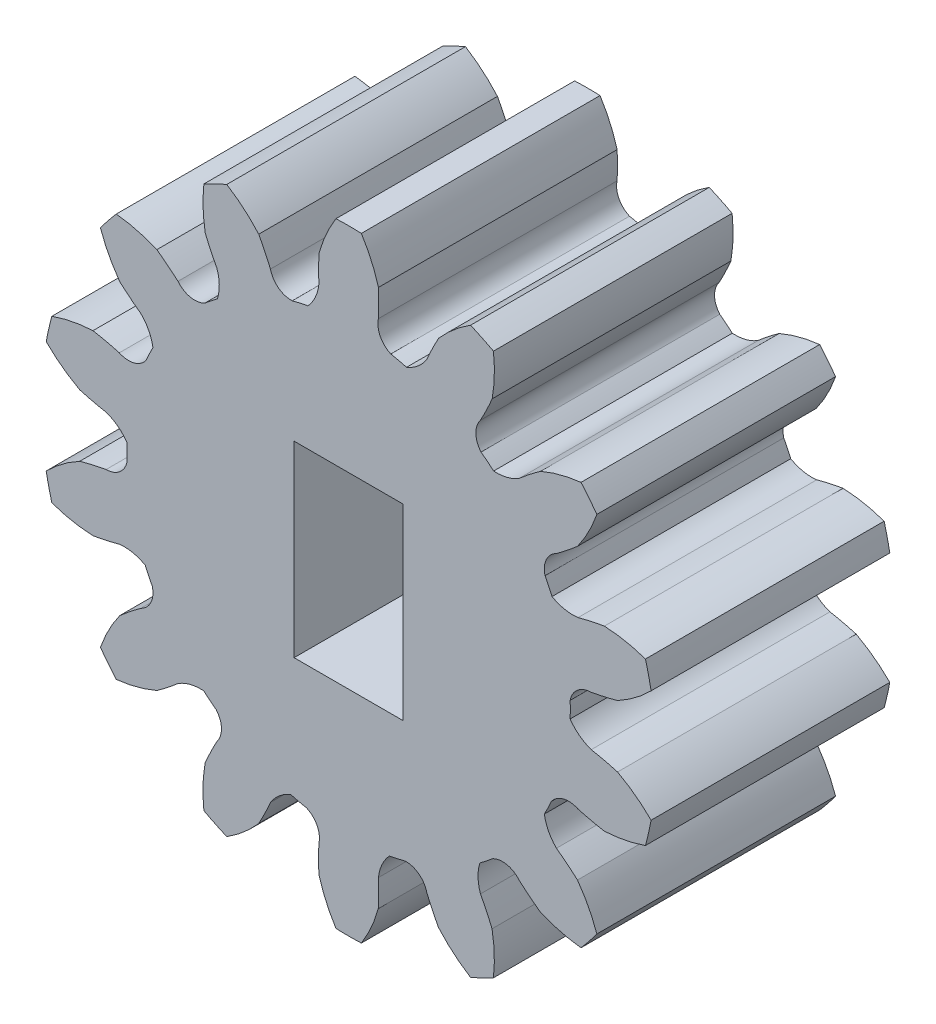
SolidWorks part; units mm, degrees
ref_plane "Front Plane" through (0, 0, 0) normal (0, 0, 1) x (1, 0, 0)
ref_plane "Top Plane" through (0, 0, 0) normal (0, 1, 0) x (1, 0, 0)
ref_plane "Right Plane" through (0, 0, 0) normal (1, 0, 0) x (0, 0, -1)
ref_plane "Plane1" through (0, 0, 20) normal (0, 0, 1) x (1, 0, 0)
ref_plane "Plane2" through (0, 0, 27) normal (0, 0, 1) x (1, 0, 0)
sketch "Sketch1" plane through (0, 0, 20) normal (0, 0, 1) x (1, 0, 0)
  circle A1 centre (0, 20.9252) radius 6.5
  dimension "D1" = 13
sketch "Sketch2" plane through (0, 0, 20) normal (0, 0, 1) x (1, 0, 0)
  arc A0 (-0.3724, 29.9378) -> (0.3724, 29.9378) centre (0, 20.8103) cw
  arc A1 (0.3724, 29.9378) -> (0.873, 28.8151) centre (-3.1544, 27.6923) cw
  arc A2 (0.873, 28.8151) -> (0.873, 28.0231) centre (-7.7307, 28.4191) cw
  arc A3 (0.873, 28.0231) -> (1.2364, 27.3066) centre (1.4883, 27.8847) ccw
  circle A4 centre (0, 20.9252) radius 6.5 construction
  arc A5 (-0.873, 28.0231) -> (-1.1929, 27.3148) centre (-2.1071, 28.1541) cw
  arc A6 (-0.868, 28.8151) -> (-0.873, 28.0231) centre (7.003, 28.369) ccw
  arc A7 (-0.3724, 29.9378) -> (-0.868, 28.8151) centre (3.1633, 27.7064) ccw
  arc A8 (-1.1929, 27.3148) -> (1.2364, 27.3066) centre (0, 20.9252) cw
  arc A9 (1.6976, 27.1996) -> (3.8827, 26.1381) centre (0, 20.9252) cw
  arc A10 (3.8662, 26.9414) -> (3.8827, 26.1381) centre (4.3605, 26.5498) ccw
  arc A11 (4.2099, 27.655) -> (3.8662, 26.9414) centre (-3.7136, 31.0312) cw
  arc A12 (4.246, 28.8837) -> (4.2099, 27.655) centre (0.0942, 28.3908) cw
  arc A13 (3.5748, 29.2069) -> (4.246, 28.8837) centre (-0.0499, 20.8217) cw
  arc A14 (3.5748, 29.2069) -> (2.6413, 28.4104) centre (5.7923, 25.6624) ccw
  arc A15 (2.6413, 28.4104) -> (2.2931, 27.699) centre (9.5392, 24.5934) ccw
  arc A16 (2.2931, 27.699) -> (1.6976, 27.1996) centre (1.238, 28.3525) cw
  arc A17 (4.2518, 25.8417) -> (5.76, 23.9372) centre (0, 20.9252) cw
  arc A18 (6.0937, 24.6682) -> (5.76, 23.9372) centre (6.3691, 24.1008) ccw
  arc A19 (6.7129, 25.162) -> (6.0937, 24.6682) centre (1.039, 31.6417) cw
  arc A20 (7.2785, 26.2533) -> (6.7129, 25.162) centre (3.324, 27.6106) cw
  arc A21 (6.8141, 26.8357) -> (7.2785, 26.2533) centre (-0.0899, 20.8536) cw
  arc A22 (6.8141, 26.8357) -> (5.6274, 26.5231) centre (7.2741, 22.6801) ccw
  arc A23 (5.6274, 26.5231) -> (5.005, 26.0332) centre (10.1861, 20.0912) ccw
  arc A24 (5.005, 26.0332) -> (4.2518, 25.8417) centre (4.338, 27.0798) cw
  arc A25 (5.964, 23.51) -> (6.4965, 21.1398) centre (0, 20.9252) cw
  arc A26 (7.1142, 21.6535) -> (6.4965, 21.1398) centre (7.1162, 21.0229) ccw
  arc A27 (7.8864, 21.8298) -> (7.1142, 21.6535) centre (5.5858, 30.1296) cw
  arc A28 (8.8695, 22.5676) -> (7.8864, 21.8298) centre (5.8955, 25.5063) cw
  arc A29 (8.7037, 23.2938) -> (8.8695, 22.5676) centre (-0.112, 20.8997) cw
  arc A30 (8.7037, 23.2938) -> (7.499, 23.5271) centre (7.3151, 19.3502) ccw
  arc A31 (7.499, 23.5271) -> (6.7257, 23.3558) centre (8.8155, 15.7542) ccw
  arc A32 (6.7257, 23.3558) -> (5.964, 23.51) centre (6.5788, 24.5881) cw
  arc A33 (6.4948, 20.6664) -> (5.9462, 18.2998) centre (0, 20.9252) cw
  arc A34 (6.7257, 18.4947) -> (5.9462, 18.2998) centre (6.4538, 17.9257) ccw
  arc A35 (7.4978, 18.3184) -> (6.7257, 18.4947) centre (9.0263, 26.7945) cw
  arc A36 (8.7037, 18.5567) -> (7.4978, 18.3184) centre (7.2993, 22.4947) cw
  arc A37 (8.8695, 19.2829) -> (8.7037, 18.5567) centre (-0.112, 20.9508) cw
  arc A38 (8.8695, 19.2829) -> (7.8852, 20.0158) centre (5.9073, 16.3323) ccw
  arc A39 (7.8852, 20.0158) -> (7.1142, 20.1969) centre (5.6988, 12.4414) ccw
  arc A40 (7.1142, 20.1969) -> (6.4948, 20.6664) centre (7.5165, 21.371) cw
  arc A41 (5.7394, 17.874) -> (4.2182, 15.9799) centre (0, 20.9252) cw
  arc A42 (5.005, 15.8172) -> (4.2182, 15.9799) centre (4.5132, 15.4225) ccw
  arc A43 (5.6243, 15.3234) -> (5.005, 15.8172) centre (10.679, 22.297) cw
  arc A44 (6.8141, 15.0148) -> (5.6243, 15.3234) centre (7.2574, 19.1722) cw
  arc A45 (7.2785, 15.5972) -> (6.8141, 15.0148) centre (-0.0899, 20.9969) cw
  arc A46 (7.2785, 15.5972) -> (6.7098, 16.6846) centre (3.3295, 14.224) ccw
  arc A47 (6.7098, 16.6846) -> (6.0937, 17.1823) centre (1.4535, 10.8089) ccw
  arc A48 (6.0937, 17.1823) -> (5.7394, 17.874) centre (6.9655, 18.0655) cw
  arc A49 (3.8471, 15.686) -> (1.6548, 14.6394) centre (0, 20.9252) cw
  arc A50 (2.2931, 14.1515) -> (1.6548, 14.6394) centre (1.6787, 14.0092) ccw
  arc A51 (2.6367, 13.4379) -> (2.2931, 14.1515) centre (10.2166, 17.5277) cw
  arc A52 (3.5748, 12.6436) -> (2.6367, 13.4379) centre (5.7781, 16.1969) cw
  arc A53 (4.246, 12.9668) -> (3.5748, 12.6436) centre (-0.0499, 21.0288) cw
  arc A54 (4.246, 12.9668) -> (4.2053, 14.1933) centre (0.0922, 13.4431) ccw
  arc A55 (4.2053, 14.1933) -> (3.8662, 14.909) centre (-3.0798, 11.1801) ccw
  arc A56 (3.8662, 14.909) -> (3.8471, 15.686) centre (5.035, 15.3265) cw
  arc A57 (1.1929, 14.5356) -> (-1.2364, 14.5439) centre (0, 20.9252) cw
  arc A58 (-0.873, 13.8273) -> (-1.2364, 14.5439) centre (-1.4883, 13.9658) ccw
  arc A59 (-0.873, 13.0353) -> (-0.873, 13.8273) centre (7.7307, 13.4313) cw
  arc A60 (-0.3724, 11.9127) -> (-0.873, 13.0353) centre (3.1544, 14.1581) cw
  arc A61 (0.3724, 11.9127) -> (-0.3724, 11.9127) centre (0, 21.0402) cw
  arc A62 (0.3724, 11.9127) -> (0.868, 13.0353) centre (-3.1633, 14.144) ccw
  arc A63 (0.868, 13.0353) -> (0.873, 13.8273) centre (-7.003, 13.4814) ccw
  arc A64 (0.873, 13.8273) -> (1.1929, 14.5356) centre (2.1071, 13.6964) cw
  arc A65 (-1.6976, 14.6508) -> (-3.8827, 15.7123) centre (0, 20.9252) cw
  arc A66 (-3.8662, 14.909) -> (-3.8827, 15.7123) centre (-4.3605, 15.3007) ccw
  arc A67 (-4.2099, 14.1955) -> (-3.8662, 14.909) centre (3.7136, 10.8192) cw
  arc A68 (-4.246, 12.9668) -> (-4.2099, 14.1955) centre (-0.0942, 13.4597) cw
  arc A69 (-3.5748, 12.6436) -> (-4.246, 12.9668) centre (0.0499, 21.0288) cw
  arc A70 (-3.5748, 12.6436) -> (-2.6413, 13.4401) centre (-5.7923, 16.1881) ccw
  arc A71 (-2.6413, 13.4401) -> (-2.2931, 14.1515) centre (-9.5392, 17.2571) ccw
  arc A72 (-2.2931, 14.1515) -> (-1.6976, 14.6508) centre (-1.238, 13.498) cw
  arc A73 (-4.2518, 16.0087) -> (-5.76, 17.9132) centre (0, 20.9252) cw
  arc A74 (-6.0937, 17.1823) -> (-5.76, 17.9132) centre (-6.3691, 17.7496) ccw
  arc A75 (-6.7129, 16.6885) -> (-6.0937, 17.1823) centre (-1.039, 10.2088) cw
  arc A76 (-7.2785, 15.5972) -> (-6.7129, 16.6885) centre (-3.324, 14.2398) cw
  arc A77 (-6.8141, 15.0148) -> (-7.2785, 15.5972) centre (0.0899, 20.9969) cw
  arc A78 (-6.8141, 15.0148) -> (-5.6274, 15.3274) centre (-7.2741, 19.1704) ccw
  arc A79 (-5.6274, 15.3274) -> (-5.005, 15.8172) centre (-10.1861, 21.7593) ccw
  arc A80 (-5.005, 15.8172) -> (-4.2518, 16.0087) centre (-4.338, 14.7707) cw
  arc A81 (-5.964, 18.3404) -> (-6.4965, 20.7107) centre (0, 20.9252) cw
  arc A82 (-7.1142, 20.1969) -> (-6.4965, 20.7107) centre (-7.1162, 20.8276) ccw
  arc A83 (-7.8864, 20.0207) -> (-7.1142, 20.1969) centre (-5.5858, 11.7208) cw
  arc A84 (-8.8695, 19.2829) -> (-7.8864, 20.0207) centre (-5.8955, 16.3441) cw
  arc A85 (-8.7037, 18.5567) -> (-8.8695, 19.2829) centre (0.112, 20.9508) cw
  arc A86 (-8.7037, 18.5567) -> (-7.499, 18.3234) centre (-7.3151, 22.5003) ccw
  arc A87 (-7.499, 18.3234) -> (-6.7257, 18.4947) centre (-8.8155, 26.0963) ccw
  arc A88 (-6.7257, 18.4947) -> (-5.964, 18.3404) centre (-6.5788, 17.2624) cw
  arc A89 (-6.4948, 21.1841) -> (-5.9462, 23.5506) centre (0, 20.9252) cw
  arc A90 (-6.7257, 23.3558) -> (-5.9462, 23.5506) centre (-6.4538, 23.9248) ccw
  arc A91 (-7.4978, 23.532) -> (-6.7257, 23.3558) centre (-9.0263, 15.0559) cw
  arc A92 (-8.7037, 23.2938) -> (-7.4978, 23.532) centre (-7.2993, 19.3558) cw
  arc A93 (-8.8695, 22.5676) -> (-8.7037, 23.2938) centre (0.112, 20.8997) cw
  arc A94 (-8.8695, 22.5676) -> (-7.8852, 21.8347) centre (-5.9073, 25.5182) ccw
  arc A95 (-7.8852, 21.8347) -> (-7.1142, 21.6535) centre (-5.6988, 29.4091) ccw
  arc A96 (-7.1142, 21.6535) -> (-6.4948, 21.1841) centre (-7.5165, 20.4795) cw
  arc A97 (-5.7394, 23.9764) -> (-4.2182, 25.8706) centre (0, 20.9252) cw
  arc A98 (-5.005, 26.0332) -> (-4.2182, 25.8706) centre (-4.5132, 26.428) ccw
  arc A99 (-5.6243, 26.5271) -> (-5.005, 26.0332) centre (-10.679, 19.5535) cw
  arc A100 (-6.8141, 26.8357) -> (-5.6243, 26.5271) centre (-7.2574, 22.6783) cw
  arc A101 (-7.2785, 26.2533) -> (-6.8141, 26.8357) centre (0.0899, 20.8536) cw
  arc A102 (-7.2785, 26.2533) -> (-6.7098, 25.1659) centre (-3.3295, 27.6264) ccw
  arc A103 (-6.7098, 25.1659) -> (-6.0937, 24.6682) centre (-1.4535, 31.0415) ccw
  arc A104 (-6.0937, 24.6682) -> (-5.7394, 23.9764) centre (-6.9655, 23.7849) cw
  arc A105 (-3.8471, 26.1645) -> (-1.6548, 27.2111) centre (0, 20.9252) cw
  arc A106 (-2.2931, 27.699) -> (-1.6548, 27.2111) centre (-1.6787, 27.8412) ccw
  arc A107 (-2.6367, 28.4126) -> (-2.2931, 27.699) centre (-10.2166, 24.3228) cw
  arc A108 (-3.5748, 29.2069) -> (-2.6367, 28.4126) centre (-5.7781, 25.6535) cw
  arc A109 (-4.246, 28.8837) -> (-3.5748, 29.2069) centre (0.0499, 20.8217) cw
  arc A110 (-4.246, 28.8837) -> (-4.2053, 27.6572) centre (-0.0922, 28.4074) ccw
  arc A111 (-4.2053, 27.6572) -> (-3.8662, 26.9414) centre (3.0798, 30.6704) ccw
  arc A112 (-3.8662, 26.9414) -> (-3.8471, 26.1645) centre (-5.035, 26.524) cw
  point P4 (-0.873, 28.0231)
  point P5 (-0.365, 30.5476)
  point P192 (0, 20.9252)
  point P216 (-0.873, 28.8151)
  point P217 (0.5203, 30.8311)
  point P218 (-0.1848, 30.8311)
  point P219 (0.9658, 29.2008)
  point P220 (1.0468, 28.2425)
  point P221 (1.0468, 28.8151)
  point P222 (1.0468, 28.0231)
  point P223 (1.238, 27.3062)
  point P224 (0.3782, 30.4646)
  point P225 (-0.4116, 30.4646)
  point P226 (-0.2517, 30.4646)
  point P227 (0.873, 28.8151)
  point P228 (0.873, 28.1541)
  point P229 (1.238, 27.3148)
  point P230 (0.873, 28.0231)
  point P231 (0.3078, 30.0008)
  point P232 (-0.3724, 29.9378)
  point P233 (0.3724, 29.9378)
  point P234 (0, 0)
  dimension "D1" = 14
extrude "Boss-Extrude1" add sketch "Sketch2" along normal blind 7
sketch "Sketch3" plane through (0, 0, 27) normal (0, 0, 1) x (1, 0, 0)
  line L0 (-3.9726, 20.9252) -> (15.3734, 20.9252) construction
  line L1 (0, 24.8978) -> (0, 8.7425) construction
  line L3 (-1.6, 23.6752) -> (1.6, 23.6752)
  line L4 (-1.6, 23.6752) -> (-1.6, 18.1752)
  line L5 (-1.6, 18.1752) -> (1.6, 18.1752)
  line L6 (1.6, 23.6752) -> (1.6, 18.1752)
  dimension "D1" = 3.2
  dimension "D2" = 5.5
  dimension "D3" = 1.6
  dimension "D4" = 2.75
extrude "Boss-Extrude2" add sketch "Sketch1" along normal blind 7
extrude "Cut-Extrude1" cut sketch "Sketch3" against normal blind 6
